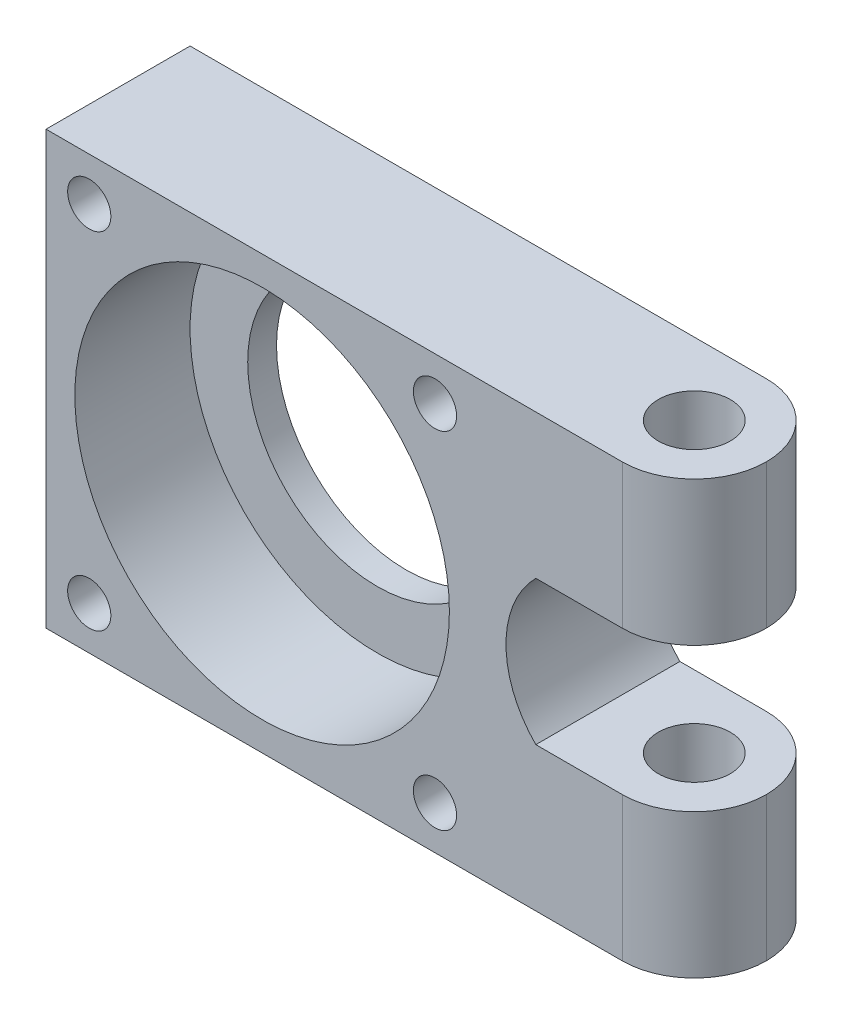
SolidWorks part; units mm, degrees
ref_plane "Plano frontal" through (0, 0, 0) normal (0, 0, 1) x (1, 0, 0)
ref_plane "Plano superior" through (0, 0, 0) normal (0, 1, 0) x (1, 0, 0)
ref_plane "Plano direito" through (0, 0, 0) normal (1, 0, 0) x (0, 0, -1)
sketch "Esboço1" plane through (0, 0, 0) normal (0, 0, 1) x (1, 0, 0)
  line L0 (22.5, 15) -> (-22.5, -15) construction
  line L1 (-22.5, 15) -> (22.5, 15)
  line L2 (-22.5, 15) -> (-22.5, -15)
  line L3 (-22.5, -15) -> (22.5, -15)
  line L4 (22.5, 15) -> (22.5, 5)
  line L5 (22.5, -5) -> (22.5, -15)
  line L6 (11.5, 5) -> (22.5, 5)
  line L7 (11.5, 5) -> (11.5, -5)
  line L8 (11.5, -5) -> (22.5, -5)
  dimension "D1" = 30
  dimension "D2" = 45
  dimension "D3" = 10
  dimension "D4" = 10
  dimension "D5" = 11
extrude "Ressalto-extrusão1" add sketch "Esboço1" along normal blind 10
sketch "Esboço2" plane through (0, -15, 0) normal (0, -1, 0) x (1, 0, 0)
  line L0 (22.5, 10) -> (22.5, 0) construction
  line L1 (-22.5, 0) -> (22.5, 0) construction
  circle A0 centre (17.5, 5) radius 2.5
  point P0 (17.5, 5)
  dimension "D3" = 5
  dimension "D1" = 5
  dimension "D2" = 5
extrude "Corte-extrusão1" cut sketch "Esboço2" against normal up to surface (30 mm away) up to face at (0, 15, 5)
sketch "Esboço4" plane through (0, 0, 10) normal (0, 0, 1) x (1, 0, 0)
  line L0 (11.5, 5) -> (11.5, -5)
  arc A0 (11.5, -5) -> (11.5, 5) centre (16.5, 0) cw
  dimension "D1" = 7.0711
extrude "Corte-extrusão2" cut sketch "Esboço4" against normal blind 10
sketch "Esboço5" plane through (0, 0, 10) normal (0, 0, 1) x (1, 0, 0)
  line L0 (-22.5, 15) -> (-22.5, -15) construction
  line L1 (-22.5, -15) -> (22.5, -15) construction
  circle A0 centre (-7.5, 0) radius 13
  point P6 (-4.7552, 9.1636)
  dimension "D3" = 26
  dimension "D1" = 15
  dimension "D2" = 15
extrude "Corte-extrusão3" cut sketch "Esboço5" against normal blind 8
sketch "Esboço6" plane through (0, 0, 2) normal (0, 0, 1) x (1, 0, 0)
  circle A0 centre (-7.5, 0) radius 9
  dimension "D1" = 18
extrude "Corte-extrusão4" cut sketch "Esboço6" against normal through all
fillet "Filete1" radius 5 4 edges at (22.5, 10, 0) (22.5, 10, 10) (22.5, -10, 0) (22.5, -10, 10)
sketch "Esboço7" plane through (0, 0, 10) normal (0, 0, 1) x (1, 0, 0)
  line L0 (-22.5, 15) -> (-22.5, -15) construction
  line L1 (-22.5, -15) -> (17.5, -15) construction
  line L2 (-22.5, 0) -> (-12.528, 0) construction
  line L3 (-12.528, 0) -> (-7.5, -3.8019) construction
  line L4 (-7.5, -3.8019) -> (-7.5, -15) construction
  circle A0 centre (-19.5, -12) radius 1.5
  circle A1 centre (-19.5, 12) radius 1.5
  circle A2 centre (4.5, 12) radius 1.5
  circle A3 centre (4.5, -12) radius 1.5
  dimension "D3" = 3
  dimension "D1" = 3
  dimension "D2" = 3
  dimension "D4" = 15
extrude "Corte-extrusão5" cut sketch "Esboço7" against normal blind 10
